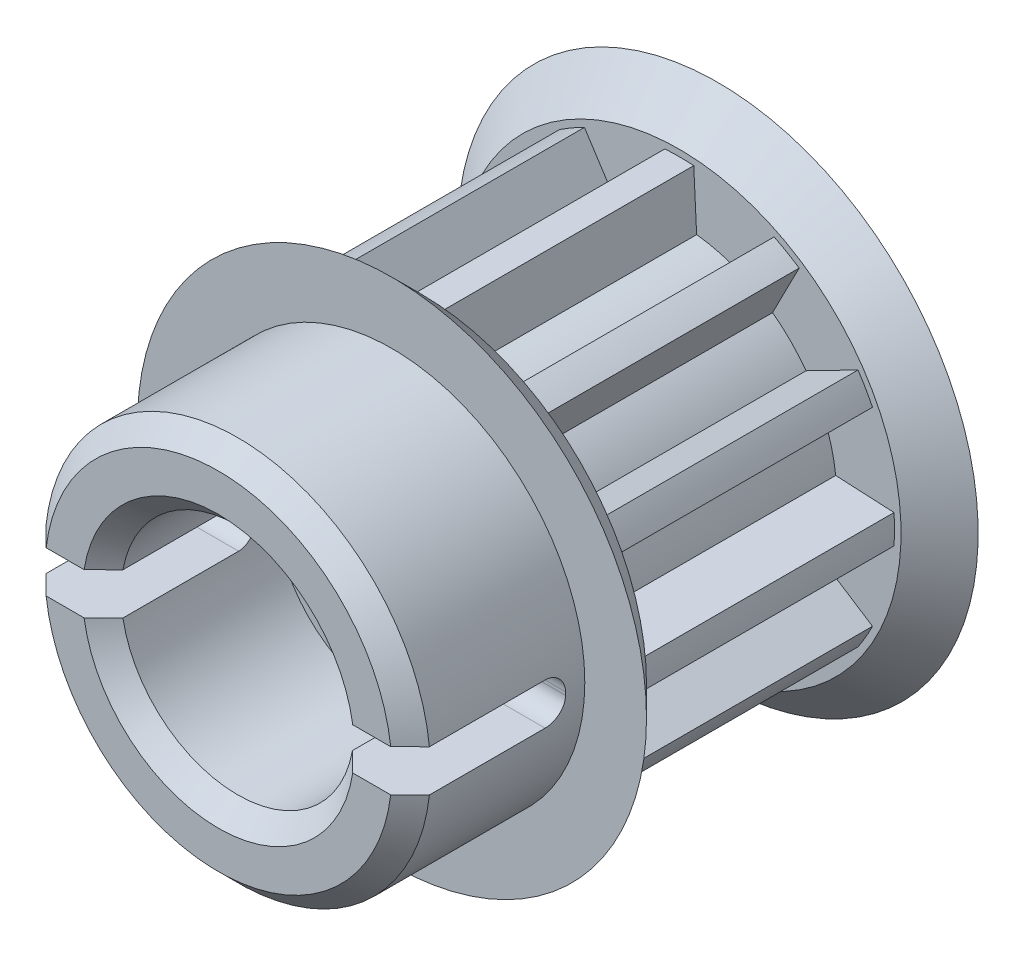
SolidWorks part; units mm, degrees
material "ABS"
ref_plane "Alzado" through (0, 0, 0) normal (0, 0, 1) x (1, 0, 0)
ref_plane "Planta" through (0, 0, 0) normal (0, 1, 0) x (1, 0, 0)
ref_plane "Vista lateral" through (0, 0, 0) normal (1, 0, 0) x (0, 0, -1)
sketch "Croquis1" plane through (0, 0, 0) normal (0, 0, 1) x (1, 0, 0)
  line L0 (0, 0) -> (0, 4.6049) construction
  line L1 (0.375, 5.5679) -> (0.45, 4.0556)
  line L2 (-0.375, 5.5679) -> (-0.45, 4.0556)
  line L3 (2.4592, 5.0094) -> (1.6381, 3.7373)
  line L4 (3.1087, 4.6344) -> (2.4175, 3.2873)
  line L5 (4.6344, 3.1087) -> (3.2873, 2.4175)
  line L6 (5.0094, 2.4592) -> (3.7373, 1.6381)
  line L7 (5.5679, 0.375) -> (4.0556, 0.45)
  line L8 (5.5679, -0.375) -> (4.0556, -0.45)
  line L9 (5.0094, -2.4592) -> (3.7373, -1.6381)
  line L10 (4.6344, -3.1087) -> (3.2873, -2.4175)
  line L11 (3.1087, -4.6344) -> (2.4175, -3.2873)
  line L12 (2.4592, -5.0094) -> (1.6381, -3.7373)
  line L13 (0.375, -5.5679) -> (0.45, -4.0556)
  line L14 (-0.375, -5.5679) -> (-0.45, -4.0556)
  line L15 (-2.4592, -5.0094) -> (-1.6381, -3.7373)
  line L16 (-3.1087, -4.6344) -> (-2.4175, -3.2873)
  line L17 (-4.6344, -3.1087) -> (-3.2873, -2.4175)
  line L18 (-5.0094, -2.4592) -> (-3.7373, -1.6381)
  line L19 (-5.5679, -0.375) -> (-4.0556, -0.45)
  line L20 (-5.5679, 0.375) -> (-4.0556, 0.45)
  line L21 (-5.0094, 2.4592) -> (-3.7373, 1.6381)
  line L22 (-4.6344, 3.1087) -> (-3.2873, 2.4175)
  line L23 (-3.1087, 4.6344) -> (-2.4175, 3.2873)
  line L24 (-2.4592, 5.0094) -> (-1.6381, 3.7373)
  circle A0 centre (0, 0) radius 1.8
  arc A1 (1.6381, 3.7373) -> (0.45, 4.0556) centre (0, 0) ccw
  arc A2 (3.1087, 4.6344) -> (2.4592, 5.0094) centre (0, 0) ccw
  arc A3 (5.0094, 2.4592) -> (4.6344, 3.1087) centre (0, 0) ccw
  arc A4 (5.5679, -0.375) -> (5.5679, 0.375) centre (0, 0) ccw
  arc A5 (4.6344, -3.1087) -> (5.0094, -2.4592) centre (0, 0) ccw
  arc A6 (2.4592, -5.0094) -> (3.1087, -4.6344) centre (0, 0) ccw
  arc A7 (-0.375, -5.5679) -> (0.375, -5.5679) centre (0, 0) ccw
  arc A8 (-3.1087, -4.6344) -> (-2.4592, -5.0094) centre (0, 0) ccw
  arc A9 (-5.0094, -2.4592) -> (-4.6344, -3.1087) centre (0, 0) ccw
  arc A10 (-5.5679, 0.375) -> (-5.5679, -0.375) centre (0, 0) ccw
  arc A11 (-4.6344, 3.1087) -> (-5.0094, 2.4592) centre (0, 0) ccw
  arc A12 (-2.4592, 5.0094) -> (-3.1087, 4.6344) centre (0, 0) ccw
  arc A13 (0.375, 5.5679) -> (-0.375, 5.5679) centre (0, 0) ccw
  arc A14 (3.2873, 2.4175) -> (2.4175, 3.2873) centre (0, 0) ccw
  arc A15 (4.0556, 0.45) -> (3.7373, 1.6381) centre (0, 0) ccw
  arc A16 (3.7373, -1.6381) -> (4.0556, -0.45) centre (0, 0) ccw
  arc A17 (2.4175, -3.2873) -> (3.2873, -2.4175) centre (0, 0) ccw
  arc A18 (0.45, -4.0556) -> (1.6381, -3.7373) centre (0, 0) ccw
  arc A19 (-1.6381, -3.7373) -> (-0.45, -4.0556) centre (0, 0) ccw
  arc A20 (-3.2873, -2.4175) -> (-2.4175, -3.2873) centre (0, 0) ccw
  arc A21 (-4.0556, -0.45) -> (-3.7373, -1.6381) centre (0, 0) ccw
  arc A22 (-3.7373, 1.6381) -> (-4.0556, 0.45) centre (0, 0) ccw
  arc A23 (-2.4175, 3.2873) -> (-3.2873, 2.4175) centre (0, 0) ccw
  arc A24 (-0.45, 4.0556) -> (-1.6381, 3.7373) centre (0, 0) ccw
  dimension "D1" = 0.9
  dimension "D2" = 3.6
  dimension "D4" = 1.5
  dimension "D3" = 0.75
  dimension "D6" = 1.23
  dimension "D5" = 12
extrude "Saliente-Extruir1" add sketch "Croquis1" along normal blind 6.7
sketch "Croquis2" plane through (0, 0, 6.7) normal (0, 0, 1) x (1, 0, 0)
  circle A0 centre (0, 0) radius 3.025
  circle A1 centre (0, 0) radius 5
  dimension "D1" = 10
  dimension "D2" = 6.05
extrude "Saliente-Extruir2" add sketch "Croquis2" along normal blind 5.25
chamfer "Chaflán1" distance 0.5 angle 45 1 edges at (5, 0, 11.95)
sketch "Croquis3" plane through (0, 0, 0) normal (0, 0, -1) x (-1, 0, 0)
  circle A0 centre (0, 0) radius 1.8
  circle A1 centre (0, 0) radius 6.75
  circle A2 centre (0, 0) radius 1.8 construction
  dimension "D1" = 13.5
extrude "Saliente-Extruir3" add sketch "Croquis3" along normal blind 1
chamfer "Chaflán2" distance 0.5 angle 45 1 edges at (3.025, 0, 11.95)
sketch "Croquis4" plane through (0, 0, 6.7) normal (0, 0, 1) x (1, 0, 0)
  circle A0 centre (0, 0) radius 1.8
  circle A1 centre (0, 0) radius 4.8926
  circle A2 centre (0, 0) radius 1.8 construction
extrude "Saliente-Extruir4" add sketch "Croquis4" along normal blind 0.1
chamfer "Chaflán3" distance 0.5 angle 45 12 edges at (3.9415, 1.0561, 6.7) (2.8853, 2.8853, 6.7) (1.0561, 3.9415, 6.7) (-1.0561, 3.9415, 6.7) (-2.8853, 2.8853, 6.7) (-3.9415, -1.0561, 6.7) (-3.9415, 1.0561, 6.7) (-2.8853, -2.8853, 6.7) (-1.0561, -3.9415, 6.7) (1.0561, -3.9415, 6.7) (2.8853, -2.8853, 6.7) (3.9415, -1.0561, 6.7)
chamfer "Chaflán4" distance 1 angle 45 1 edges at (-6.75, 0, 0)
sketch "Croquis6" plane through (0, 0, 6.7) normal (0, 0, 1) x (1, 0, 0)
  circle A0 centre (0, 0) radius 6.75
  circle A2 centre (0, 0) radius 1.8
  circle A4 centre (0, 0) radius 1.8 construction
  dimension "D1" = 13.5
extrude "Saliente-Extruir5" add sketch "Croquis6" along normal blind 0.75
chamfer "Chaflán5" distance 0.9 angle 45 1 edges at (6.75, 0, 6.7)
sketch "Croquis8" plane through (0, 0, -1) normal (0, 0, -1) x (-1, 0, 0)
  line L1 (-1.4973, -2.3662) -> (1.3006, -2.4798)
  line L2 (1.3006, -2.4798) -> (2.7978, -0.1136)
  line L3 (2.7978, -0.1136) -> (1.4973, 2.3662)
  line L4 (1.4973, 2.3662) -> (-1.3006, 2.4798)
  line L5 (-1.3006, 2.4798) -> (-2.7978, 0.1136)
  line L6 (-2.7978, 0.1136) -> (-1.4973, -2.3662)
  circle A0 centre (0, 0) radius 2.425 construction
  dimension "D1" = 4.85
extrude "Cortar-Extruir1" cut sketch "Croquis8" against normal blind 5
chamfer "Chaflán6" distance 1 angle 45 6 edges at (-0.0984, 2.423, -1) (2.0492, 1.2967, -1) (2.1476, -1.1263, -1) (0.0984, -2.423, -1) (-2.0492, -1.2967, -1) (-2.1476, 1.1263, -1)
chamfer "Chaflán7" distance 1 angle 45 1 edges at (-1.8, 0, 4)
sketch "Croquis9" plane through (0, 0, 11.95) normal (0, 0, 1) x (1, 0, 0)
  line L0 (5.7484, 0) -> (-6.3843, 0) construction
  line L1 (5.7026, -0.5408) -> (5.7026, 0.5408)
  line L2 (5.7026, 0.5408) -> (-5.9897, 0.5408)
  line L3 (-5.9897, 0.5408) -> (-5.9897, -0.5408)
  line L4 (-5.9897, -0.5408) -> (5.7026, -0.5408)
extrude "Cortar-Extruir2" cut sketch "Croquis9" along direction (0, 0, 1) on the side against the normal blind 4
fillet "Redondeo1" radius 0.5 4 edges at (3.9735, -0.5408, 7.95) (3.9735, 0.5408, 7.95) (-3.9735, -0.5408, 7.95) (-3.9735, 0.5408, 7.95)
